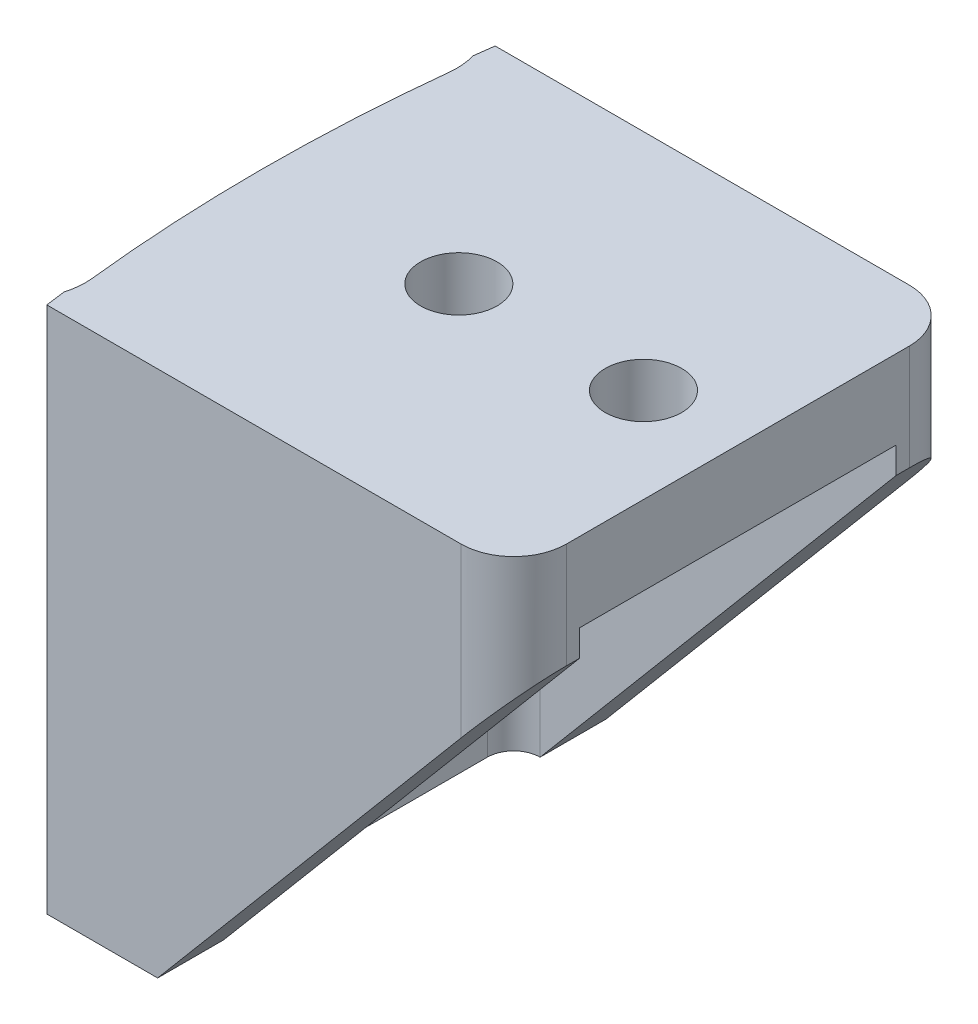
SolidWorks part; units mm, degrees
ref_plane "Front Plane" through (0, 0, 0) normal (0, 0, 1) x (1, 0, 0)
ref_plane "Top Plane" through (0, 0, 0) normal (0, 1, 0) x (1, 0, 0)
ref_plane "Right Plane" through (0, 0, 0) normal (1, 0, 0) x (0, 0, -1)
sketch "Sketch1" plane through (0, 0, 0) normal (0, 1, 0) x (1, 0, 0)
  line L0 (-123.8386, 17) -> (-88.8386, 17)
  line L1 (-88.8386, 17) -> (-88.8386, -17)
  line L2 (-88.8386, -17) -> (-123.8386, -17)
  arc A0 (-123.8386, 17) -> (-123.8386, -17) centre (0, 0) ccw
  point P8 (-88.8386, 0)
  dimension "D1" = 125
  dimension "D2" = 34
  dimension "D3" = 35
extrude "Boss-Extrude1" add sketch "Sketch1" along normal blind 40
sketch "Sketch2" plane through (0, 0, 17) normal (0, 0, 1) x (1, 0, 0)
  line L0 (-88.8386, 0) -> (-88.8386, 32)
  line L1 (-88.8386, 40) -> (-88.8386, 0) construction
  line L2 (-88.8386, 32) -> (-115.8386, 0)
  line L3 (-123.8386, 0) -> (-88.8386, 0) construction
  line L4 (-115.8386, 0) -> (-88.8386, 0)
  dimension "D1" = 8
  dimension "D2" = 8
extrude "Cut-Extrude1" cut sketch "Sketch2" against normal up to next
sketch "Sketch3" plane through (0, 0, 0) normal (0, -1, 0) x (1, 0, 0)
  line L1 (-136.2821, 0) -> (-72.7464, 0) construction
  line L2 (-117.8386, 12) -> (-88.8386, 12)
  line L3 (-88.8386, -17) -> (-88.8386, 17) construction
  line L4 (-88.8386, 17) -> (-115.8386, 17) construction
  line L6 (-117.8386, -12) -> (-88.8386, -12)
  line L7 (-88.8386, -12) -> (-88.8386, 12)
  line L8 (-115.8386, -17) -> (-88.8386, -17) construction
  line L9 (-117.8386, -12) -> (-117.8386, 12)
  dimension "D1" = 5
  dimension "D2" = 6
  dimension "D3" = 5
extrude "Cut-Extrude2" cut sketch "Sketch3" against normal blind 34
ref_plane "Plane1" through (0, 20, 0) normal (0, 1, 0) x (1, 0, 0)
sketch "Sketch6" plane through (0, 40, 0) normal (0, 1, 0) x (1, 0, 0)
  line L1 (-130.8576, 0) -> (-91.2124, 0) construction
  circle A1 centre (-110, 0) radius 2.9
  circle A2 centre (-96, 0) radius 2.9
  dimension "D2" = 110
  dimension "D1" = 5.8
  dimension "D3" = 14
extrude "Cut-Extrude3" cut sketch "Sketch6" against normal blind 31
fillet "Fillet2" radius 4 2 edges at (-88.8386, 36, 17) (-88.8386, 36, -17)
sketch "Sketch8" plane through (0, 40, 0) normal (0, 1, 0) x (1, 0, 0)
  line L0 (-123.8386, 17) -> (-124.2423, 17)
  line L1 (-124.4384, 15.5) -> (-124.0353, 15.5)
  line L2 (-136.7607, 0) -> (-86.0271, 0) construction
  line L3 (-124.4384, -15.5) -> (-124.0353, -15.5)
  line L4 (-123.8386, -17) -> (-124.2423, -17)
  arc A0 (-123.8386, 17) -> (-123.8386, -17) centre (0, 0) ccw construction
  arc A1 (-123.8386, 17) -> (-124.0353, 15.5) centre (0, 0) ccw
  arc A2 (-124.2423, 17) -> (-124.4384, 15.5) centre (0, 0) ccw
  arc A3 (-124.2349, 17.0544) -> (-124.2349, -17.0544) centre (0, 0) ccw construction
  arc A4 (-123.8386, 17) -> (-123.8386, -17) centre (0, 0) ccw construction
  arc A5 (-124.2423, -17) -> (-124.4384, -15.5) centre (0, 0) cw
  arc A6 (-123.8386, -17) -> (-124.0353, -15.5) centre (0, 0) cw
  dimension "D2" = 1.5
  dimension "D1" = 0.4
extrude "Boss-Extrude3" add sketch "Sketch8" against normal blind 40
fillet "Fillet4" radius 5 2 edges at (-124.0353, 20, 15.5) (-124.0353, 20, -15.5)
fillet "Fillet5" radius 2 2 edges at (-117.8386, 17, 12) (-117.8386, 17, -12)
